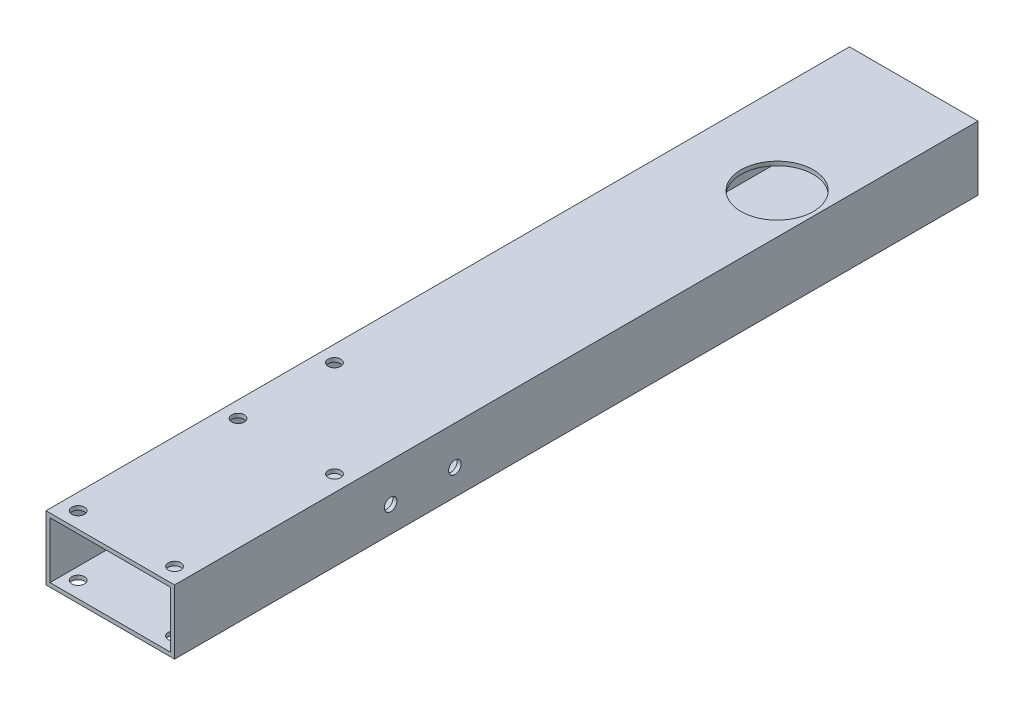
SolidWorks part; units mm, degrees
material "6061 Alloy"
ref_plane "Front Plane" through (0, 0, 0) normal (0, 0, 1) x (1, 0, 0)
ref_plane "Top Plane" through (0, 0, 0) normal (0, 1, 0) x (1, 0, 0)
ref_plane "Right Plane" through (0, 0, 0) normal (1, 0, 0) x (0, 0, -1)
sketch "Sketch1" plane through (0, 0, 0) normal (0, 0, 1) x (1, 0, 0)
  line L0 (-23.8125, 11.1125) -> (23.8125, 11.1125)
  line L2 (-25.4, 12.7) -> (25.4, 12.7)
  line L3 (-25.4, 12.7) -> (-25.4, -12.7)
  line L4 (-25.4, -12.7) -> (25.4, -12.7)
  line L5 (25.4, 12.7) -> (25.4, -12.7)
  line L10 (23.8125, 11.1125) -> (23.8125, -11.1125)
  line L11 (-23.8125, -11.1125) -> (23.8125, -11.1125)
  line L12 (-23.8125, 11.1125) -> (-23.8125, -11.1125)
  point P12 (0, 12.7)
  point P14 (25.4, 0)
  dimension "Wall Thickness" = 1.5875
  dimension "Outside Width" = 50.8
  dimension "Outside Height" = 25.4
  dimension "Inside Height" = 22.225
  dimension "Inside Width" = 47.625
sketch "Sketch2" plane through (0, 0, 0) normal (1, 0, 0) x (0, 0, -1)
  line L0 (158.75, 0) -> (-158.75, 0)
  point P4 (0, 0)
  point P7 (-158.75, 0)
  point P10 (158.75, 0)
  dimension "Length" = 317.5
sketch "Sketch3" plane through (0, 0, 0) normal (0, 0, 1) x (1, 0, 0)
  line L21 (25.4, 12.7) -> (-25.4, 12.7)
  line L22 (25.4, -12.7) -> (25.4, 12.7)
  line L23 (-25.4, -12.7) -> (25.4, -12.7)
  line L24 (-25.4, 12.7) -> (-25.4, -12.7)
  line L25 (25.4, 12.7) -> (-25.4, 12.7)
  line L26 (25.4, -12.7) -> (25.4, 12.7)
  line L27 (-25.4, -12.7) -> (25.4, -12.7)
  line L28 (-25.4, 12.7) -> (-25.4, -12.7)
  line L29 (23.8125, 11.1125) -> (-23.8125, 11.1125)
  line L30 (23.8125, -11.1125) -> (23.8125, 11.1125)
  line L31 (-23.8125, -11.1125) -> (23.8125, -11.1125)
  line L32 (-23.8125, 11.1125) -> (-23.8125, -11.1125)
  line L33 (23.8125, 11.1125) -> (-23.8125, 11.1125)
  line L34 (23.8125, -11.1125) -> (23.8125, 11.1125)
  line L35 (-23.8125, -11.1125) -> (23.8125, -11.1125)
  line L36 (-23.8125, 11.1125) -> (-23.8125, -11.1125)
  dimension "D1" = 0
  dimension "D2" = 0
extrude "Boss-Extrude1" add sketch "Sketch3" along normal up to vertex (158.75 mm away) and the other way up to vertex (158.75 mm away) up to point (0, 0, 158.75) other way up to point (0, 0, -158.75)
sketch "Drawing Reference" plane through (0, 0, 0) normal (1, 0, 0) x (0, 0, -1)
  line L0 (-158.75, 0) -> (158.75, 0) construction
  line L1 (0, -12.7) -> (0, 12.7) construction
  line L2 (-158.75, -12.7) -> (158.75, -12.7) construction
  line L5 (-158.75, 12.7) -> (158.75, 12.7) construction
  point P7 (-122.174, 0)
  point P8 (122.174, 0)
  dimension "D1" = 36.576
sketch "Sketch4" plane through (0, 12.7, 0) normal (0, 1, 0) x (1, 0, 0)
  line L0 (0, 158.75) -> (0, 95.25) construction
  line L1 (25.4, 158.75) -> (-25.4, 158.75) construction
  line L2 (0, 95.25) -> (9.525, 95.25) construction
  line L3 (0, 158.75) -> (0, -26.67) construction
  circle A1 centre (9.525, 95.25) radius 14.2875
  circle A3 centre (9.525, 95.25) radius 117.5004 construction
  dimension "D1" = 63.5
  dimension "D3" = 235.0008
  dimension "D2" = 9.525
extrude "Cut-Extrude1" cut sketch "Sketch4" against normal blind 39.37
sketch "Sketch5" plane through (-25.4, 0, 0) normal (-1, 0, 0) x (0, 0, 1)
  line L0 (73.3582, -2.425) -> (47.9582, -2.425) construction
hole_wizard "#10 Clearance Hole1" positions "Sketch6" profile "Sketch7" hole size "#10" standard "ANSI Inch" end condition through all
sketch "Sketch6" plane through (-25.4, 0, 0) normal (-1, 0, 0) x (0, 0, 1)
  point P0 (73.3582, -2.425)
  point P3 (47.9582, -2.425)
sketch "Sketch7" plane through (-25.4, -2.425, 73.3582) normal (0, 1, 0) x (0, 0, 1)
  line L0 (0, 0) -> (0, 50.8)
  line L1 (0, 50.8) -> (2.4892, 50.8)
  line L2 (2.4892, 50.8) -> (2.4892, 0)
  line L5 (2.4892, 0) -> (0, 0)
  line L11 (0, -6.35) -> (0, 107.95) construction
  dimension "Thru Hole Dia." = 4.9784
  dimension "Thru Hole Depth" = 50.8
hole_wizard "#10 Clearance Hole2" positions "Sketch8" profile "Sketch9" hole size "#10" standard "ANSI Inch" end condition through all
sketch "Sketch8" plane through (0, -12.7, 0) normal (0, -1, 0) x (-1, 0, 0)
  point P0 (19.05, -51.1131)
  point P3 (19.05, -89.2131)
  point P6 (-19.05, -89.2131)
  point P9 (-19.05, -152.4)
  point P12 (19.05, -152.4)
sketch "Sketch9" plane through (-19.05, -12.7, 51.1131) normal (1, 0, 0) x (0, 0, -1)
  line L0 (0, 0) -> (0, 25.4)
  line L1 (0, 25.4) -> (2.4892, 25.4)
  line L2 (2.4892, 25.4) -> (2.4892, 0)
  line L5 (2.4892, 0) -> (0, 0)
  line L11 (0, -6.35) -> (0, 107.95) construction
  dimension "Thru Hole Dia." = 4.9784
  dimension "Thru Hole Depth" = 25.4
equation "\"D1@Drawing Reference\"=\"Outside Width@Sketch1\" * 0.72"
